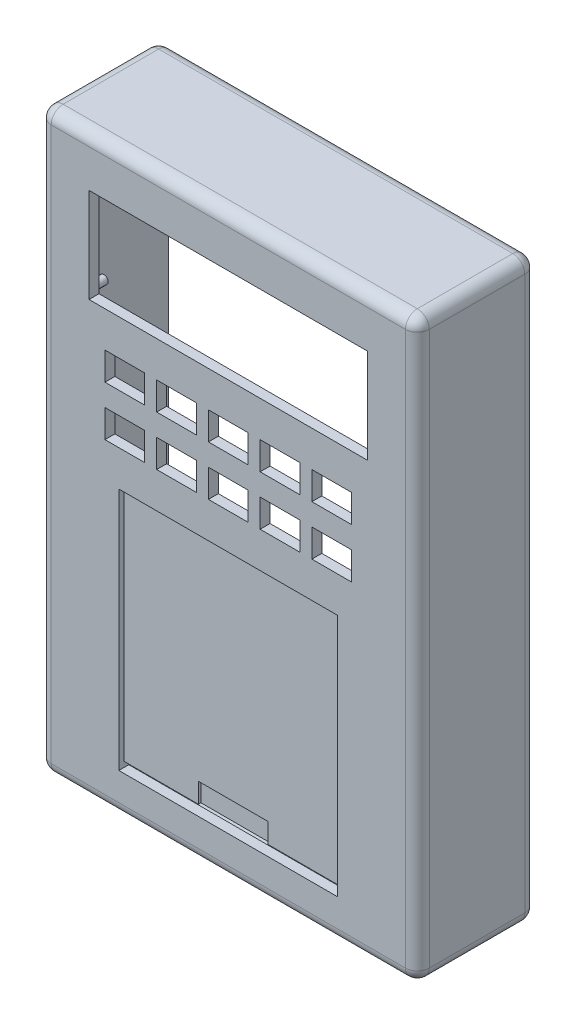
SolidWorks part; units mm, degrees
ref_plane "Front Plane" through (0, 0, 0) normal (0, 0, 1) x (1, 0, 0)
ref_plane "Top Plane" through (0, 0, 0) normal (0, 1, 0) x (1, 0, 0)
ref_plane "Right Plane" through (0, 0, 0) normal (1, 0, 0) x (0, 0, -1)
sketch "Sketch1" plane through (0, 0, 0) normal (0, 0, 1) x (1, 0, 0)
  line L1 (0, 0) -> (120.65, 0)
  line L2 (0, 0) -> (0, 184.15)
  line L3 (0, 184.15) -> (120.65, 184.15)
  line L4 (120.65, 0) -> (120.65, 184.15)
  dimension "D1" = 184.15
  dimension "D2" = 120.65
extrude "Boss-Extrude1" add sketch "Sketch1" along normal blind 38.1
fillet "Fillet1" radius 3.81 12 edges at (0, 0, 19.05) (60.325, 0, 0) (0, 92.075, 0) (120.65, 0, 19.05) (60.325, 0, 38.1) (0, 92.075, 38.1) (0, 184.15, 19.05) (60.325, 184.15, 0) (120.65, 92.075, 0) (60.325, 184.15, 38.1) (120.65, 92.075, 38.1) (120.65, 184.15, 19.05)
sketch "Sketch2" plane through (0, 0, 38.1) normal (0, 0, 1) x (1, 0, 0)
  line L0 (120.65, 180.34) -> (120.65, 3.81) construction
  line L1 (15.875, 168.275) -> (104.775, 168.275)
  line L2 (15.875, 168.275) -> (15.875, 138.1125)
  line L3 (15.875, 138.1125) -> (104.775, 138.1125)
  line L4 (104.775, 168.275) -> (104.775, 138.1125)
  line L5 (3.81, 184.15) -> (116.84, 184.15) construction
  dimension "D1" = 30.1625
  dimension "D2" = 88.9
  dimension "D3" = 15.875
  dimension "D4" = 15.875
extrude "Cut-Extrude1" cut sketch "Sketch2" against normal blind 3.175
sketch "Sketch3" plane through (0, 0, 0) normal (0, 0, -1) x (-1, 0, 0)
  line L0 (-3.81, 0) -> (-116.84, 0) construction
  line L1 (-117.475, 180.975) -> (-3.175, 180.975)
  line L2 (-117.475, 180.975) -> (-117.475, 3.175)
  line L3 (-117.475, 3.175) -> (-3.175, 3.175)
  line L4 (-3.175, 180.975) -> (-3.175, 3.175)
  line L5 (-120.65, 3.81) -> (-120.65, 180.34) construction
  dimension "D1" = 177.8
  dimension "D2" = 114.3
  dimension "D3" = 3.175
  dimension "D4" = 3.175
extrude "Cut-Extrude2" cut sketch "Sketch3" against normal blind 34.925
sketch "Sketch4" plane through (0, 0, 38.1) normal (0, 0, 1) x (1, 0, 0)
  line L0 (0, 3.81) -> (0, 180.34) construction
  line L1 (25.4, 90.4875) -> (95.25, 90.4875)
  line L2 (25.4, 90.4875) -> (25.4, 12.7)
  line L3 (25.4, 12.7) -> (95.25, 12.7)
  line L4 (95.25, 90.4875) -> (95.25, 12.7)
  line L5 (116.84, 0) -> (3.81, 0) construction
  dimension "D1" = 77.7875
  dimension "D2" = 69.85
  dimension "D3" = 25.4
  dimension "D4" = 12.7
extrude "Cut-Extrude3" cut sketch "Sketch4" against normal blind 1.5875
sketch "Sketch5" plane through (0, 0, 36.5125) normal (0, 0, 1) x (1, 0, 0)
  line L0 (0, 3.81) -> (0, 180.34) construction
  line L1 (25.4, 14.478) -> (95.25, 14.478)
  line L2 (25.4, 14.478) -> (25.4, 12.7)
  line L3 (25.4, 12.7) -> (95.25, 12.7)
  line L4 (95.25, 14.478) -> (95.25, 12.7)
  dimension "D1" = 69.85
  dimension "D2" = 1.778
  dimension "D3" = 25.4
extrude "Cut-Extrude4" cut sketch "Sketch5" against normal blind 3.175
sketch "Sketch6" plane through (0, 0, 34.925) normal (0, 0, -1) x (-1, 0, 0)
  line L2 (-117.475, 180.975) -> (-111.125, 180.975)
  line L3 (-117.475, 180.975) -> (-117.475, 174.625)
  line L4 (-117.475, 174.625) -> (-111.125, 174.625)
  line L5 (-111.125, 180.975) -> (-111.125, 174.625)
  line L6 (-3.175, 180.975) -> (-9.525, 180.975)
  line L7 (-3.175, 180.975) -> (-3.175, 174.625)
  line L8 (-3.175, 174.625) -> (-9.525, 174.625)
  line L9 (-117.475, 3.175) -> (-111.125, 3.175)
  line L10 (-117.475, 3.175) -> (-117.475, 9.525)
  line L11 (-117.475, 9.525) -> (-111.125, 9.525)
  line L12 (-111.125, 3.175) -> (-111.125, 9.525)
  line L13 (-3.175, 3.175) -> (-9.525, 3.175)
  line L14 (-3.175, 3.175) -> (-3.175, 9.525)
  line L15 (-3.175, 9.525) -> (-9.525, 9.525)
  line L16 (-9.525, 3.175) -> (-9.525, 9.525)
  line L18 (-9.525, 180.975) -> (-9.525, 174.625)
  dimension "D1" = 6.35
  dimension "D2" = 6.35
extrude "Boss-Extrude2" add sketch "Sketch6" along normal blind 31.75
sketch "Sketch7" plane through (0, 0, 34.925) normal (0, 0, -1) x (-1, 0, 0)
  line L1 (-15.875, 168.275) -> (-15.875, 138.1125) construction
  line L2 (-104.775, 168.275) -> (-15.875, 168.275) construction
  line L3 (-104.775, 138.1125) -> (-104.775, 168.275) construction
  line L4 (-15.875, 138.1125) -> (-104.775, 138.1125) construction
  circle A0 centre (-107.95, 171.45) radius 1.323
  circle A1 centre (-12.7, 171.45) radius 1.323
  circle A2 centre (-12.7, 138.1125) radius 1.323
  circle A3 centre (-107.95, 138.1125) radius 1.323
  dimension "D1" = 2.6459
  dimension "D2" = 2.6459
  dimension "D3" = 2.6459
  dimension "D4" = 2.6459
  dimension "D5" = 3.175
  dimension "D6" = 3.175
  dimension "D7" = 3.175
  dimension "D8" = 3.175
  dimension "D9" = 3.175
  dimension "D10" = 0
  dimension "D11" = 0
  dimension "D12" = 3.175
extrude "Boss-Extrude3" add sketch "Sketch7" along normal blind 4.7625
sketch "Sketch8" plane through (0, 0, 36.5125) normal (0, 0, 1) x (1, 0, 0)
  line L0 (95.25, 14.478) -> (25.4, 14.478) construction
  line L1 (49.2125, 20.828) -> (71.4375, 20.828)
  line L2 (49.2125, 20.828) -> (49.2125, 14.478)
  line L3 (49.2125, 14.478) -> (71.4375, 14.478)
  line L4 (71.4375, 20.828) -> (71.4375, 14.478)
  line L5 (0, 3.81) -> (0, 180.34) construction
  dimension "D1" = 6.35
  dimension "D2" = 22.225
  dimension "D3" = 49.2125
extrude "Cut-Extrude5" cut sketch "Sketch8" against normal blind 0.7937
sketch "Sketch9" plane through (0, 0, 3.175) normal (0, 0, -1) x (-1, 0, 0)
  line L0 (-111.125, 3.175) -> (-111.125, 9.525) construction
  line L1 (-111.125, 3.175) -> (-9.525, 3.175) construction
  line L3 (-9.525, 9.525) -> (-9.525, 3.175) construction
  line L4 (-3.175, 9.525) -> (-3.175, 174.625) construction
  line L5 (-9.525, 180.975) -> (-111.125, 180.975) construction
  line L6 (-117.475, 174.625) -> (-117.475, 9.525) construction
  line L7 (-117.475, 174.625) -> (-111.125, 174.625) construction
  circle A0 centre (-114.3, 177.8) radius 1.905
  circle A1 centre (-6.35, 177.8) radius 1.905
  circle A2 centre (-6.35, 6.35) radius 1.905
  circle A3 centre (-114.3, 6.35) radius 1.905
  dimension "D3" = 3.81
  dimension "D5" = 3.81
  dimension "D9" = 3.81
  dimension "D12" = 3.81
  dimension "D1" = 3.175
  dimension "D2" = 3.175
  dimension "D4" = 3.175
  dimension "D6" = 3.175
  dimension "D7" = 3.175
  dimension "D8" = 3.175
  dimension "D10" = 3.175
  dimension "D11" = 3.175
extrude "Cut-Extrude6" cut sketch "Sketch9" against normal blind 15.875
sketch "Sketch11" plane through (0, 0, 38.1) normal (0, 0, 1) x (1, 0, 0)
  line L0 (20.955, 126.6825) -> (20.955, 117.7925)
  line L1 (20.955, 126.6825) -> (33.655, 126.6825)
  line L2 (37.465, 126.6825) -> (50.165, 126.6825)
  line L3 (20.955, 117.7925) -> (33.655, 117.7925)
  line L4 (33.655, 126.6825) -> (33.655, 117.7925)
  line L5 (0, 3.81) -> (0, 180.34) construction
  line L6 (37.465, 126.6825) -> (37.465, 117.7925)
  line L7 (37.465, 117.7925) -> (50.165, 117.7925)
  line L8 (50.165, 126.6825) -> (50.165, 117.7925)
  line L9 (53.975, 126.6825) -> (66.675, 126.6825)
  line L10 (53.975, 126.6825) -> (53.975, 117.7925)
  line L11 (53.975, 117.7925) -> (66.675, 117.7925)
  line L12 (66.675, 126.6825) -> (66.675, 117.7925)
  line L13 (70.485, 126.6825) -> (83.185, 126.6825)
  line L14 (70.485, 126.6825) -> (70.485, 117.7925)
  line L15 (70.485, 117.7925) -> (83.185, 117.7925)
  line L16 (83.185, 126.6825) -> (83.185, 117.7925)
  line L17 (86.995, 126.6825) -> (99.695, 126.6825)
  line L18 (86.995, 126.6825) -> (86.995, 117.7925)
  line L19 (86.995, 117.7925) -> (99.695, 117.7925)
  line L20 (99.695, 126.6825) -> (99.695, 117.7925)
  line L21 (20.955, 110.8075) -> (33.655, 110.8075)
  line L22 (20.955, 110.8075) -> (20.955, 101.9175)
  line L23 (20.955, 101.9175) -> (33.655, 101.9175)
  line L24 (33.655, 110.8075) -> (33.655, 101.9175)
  line L25 (37.465, 110.8075) -> (50.165, 110.8075)
  line L26 (37.465, 110.8075) -> (37.465, 101.9175)
  line L27 (37.465, 101.9175) -> (50.165, 101.9175)
  line L28 (50.165, 110.8075) -> (50.165, 101.9175)
  line L29 (53.975, 110.8075) -> (66.675, 110.8075)
  line L30 (53.975, 110.8075) -> (53.975, 101.9175)
  line L31 (53.975, 101.9175) -> (66.675, 101.9175)
  line L32 (66.675, 110.8075) -> (66.675, 101.9175)
  line L33 (70.485, 110.8075) -> (83.185, 110.8075)
  line L34 (70.485, 110.8075) -> (70.485, 101.9175)
  line L35 (70.485, 101.9175) -> (83.185, 101.9175)
  line L36 (83.185, 110.8075) -> (83.185, 101.9175)
  line L37 (86.995, 110.8075) -> (99.695, 110.8075)
  line L38 (86.995, 110.8075) -> (86.995, 101.9175)
  line L39 (86.995, 101.9175) -> (99.695, 101.9175)
  line L40 (99.695, 110.8075) -> (99.695, 101.9175)
  line L41 (15.875, 138.1125) -> (104.775, 138.1125) construction
  line L43 (95.25, 90.4875) -> (25.4, 90.4875) construction
  dimension "D1" = 8.89
  dimension "D2" = 8.89
  dimension "D3" = 8.89
  dimension "D4" = 8.89
  dimension "D5" = 8.89
  dimension "D6" = 12.7
  dimension "D7" = 12.7
  dimension "D8" = 12.7
  dimension "D9" = 12.7
  dimension "D10" = 12.7
  dimension "D11" = 3.81
  dimension "D12" = 3.81
  dimension "D13" = 3.81
  dimension "D14" = 3.81
  dimension "D15" = 20.955
  dimension "D16" = 8.89
  dimension "D17" = 8.89
  dimension "D18" = 8.89
  dimension "D19" = 8.89
  dimension "D20" = 8.89
  dimension "D21" = 12.7
  dimension "D22" = 12.7
  dimension "D23" = 12.7
  dimension "D24" = 12.7
  dimension "D25" = 12.7
  dimension "D26" = 3.81
  dimension "D27" = 3.81
  dimension "D28" = 3.81
  dimension "D29" = 3.81
  dimension "D30" = 20.955
  dimension "D31" = 11.43
  dimension "D32" = 11.43
extrude "Cut-Extrude8" cut sketch "Sketch11" against normal through all
sketch "Sketch14" plane through (0, 0, 38.1) normal (0, 0, 1) x (1, 0, 0)
  line L0 (104.775, 168.275) -> (15.875, 168.275) construction
  line L1 (0, 3.81) -> (0, 180.34) construction
  text T1 "PIERCE COLLEGE MAA POSTER PROJECT" font "Cambria Math" height in points 12
  dimension "D1" = 4.445
  dimension "D2" = 16.51
